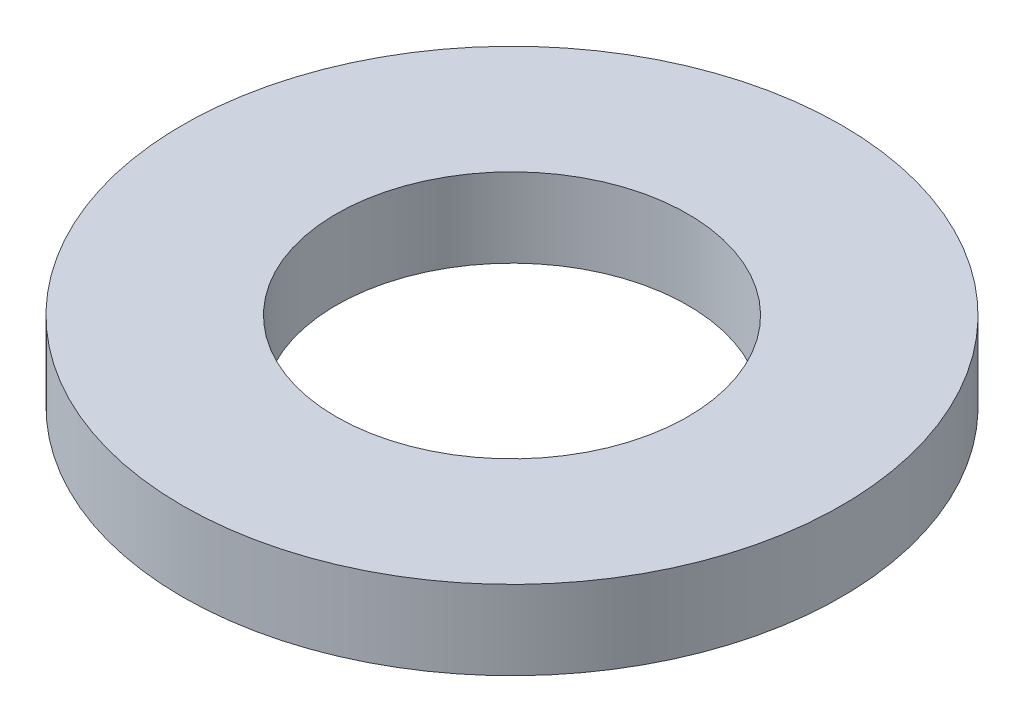
SolidWorks part; units mm, degrees
ref_plane "Front Plane" through (0, 0, 0) normal (0, 0, 1) x (1, 0, 0)
ref_plane "Top Plane" through (0, 0, 0) normal (0, 1, 0) x (1, 0, 0)
ref_plane "Right Plane" through (0, 0, 0) normal (1, 0, 0) x (0, 0, -1)
sketch "Sketch1" plane through (0, 0, 0) normal (0, 1, 0) x (1, 0, 0)
  circle A0 centre (0, 0) radius 37.5
  dimension "FLANGE_OD" = 75
extrude "Boss-Extrude1" add sketch "Sketch1" along normal blind 9
sketch "Sketch2" plane through (0, 0, 0) normal (0, 1, 0) x (1, 0, 0)
  circle A0 centre (0, 0) radius 20
  dimension "BORE_D" = 40
extrude "Cut-Extrude1" cut sketch "Sketch2" along normal through all
sketch "Sketch3" plane through (0, 9, 0) normal (0, 1, 0) x (1, 0, 0)
  circle A0 centre (0, 0) radius 15.3948 construction
  circle A1 centre (-15.3948, 0) radius 2.8705
  dimension "BOLT_D" = 5.741
  dimension "BOLT_PCD" = 30.7897
extrude "Cut-Extrude2" cut sketch "Sketch3" against normal blind 5.4929 rebuild error yes
pattern_circular "CirPattern1" count 8 over 360 rebuild error yes
